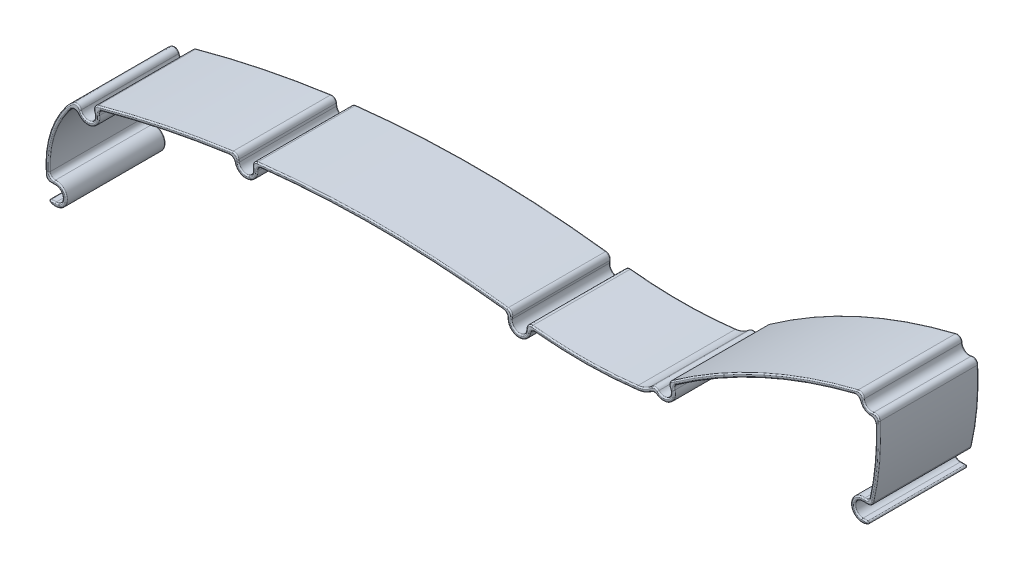
SolidWorks part; units mm, degrees
material "ﾎﾟﾘｴﾁﾚﾝﾃﾚﾌﾀﾗｰﾄ(PET)"
ref_plane "正面" through (0, 0, 0) normal (0, 0, 1) x (1, 0, 0)
ref_plane "平面" through (0, 0, 0) normal (0, 1, 0) x (1, 0, 0)
ref_plane "右側面" through (0, 0, 0) normal (1, 0, 0) x (0, 0, -1)
sketch "ｽｹｯﾁ1" plane through (0, 0, 0) normal (0, 0, 1) x (1, 0, 0)
  line L0 (152.9752, 59.7355) -> (155.8598, 58.9115) construction
  line L2 (-22.5, -19) -> (22.5, -19)
  line L6 (150, 3) -> (150, 12)
  circle A0 centre (152.9752, 59.7355) radius 3 construction
  arc A25 (145.1217, 33.8719) -> (159.4857, 98.9896) centre (52.35, 88.479) ccw
  arc A26 (159.4857, 98.9896) -> (155.8531, 101.6261) centre (156.5, 98.6967) ccw
  arc A27 (155.8531, 101.6261) -> (74.5652, 65.2106) centre (203.2901, -113.1988) ccw
  arc A28 (73.7195, 65.056) -> (74.5652, 65.2106) centre (73.98, 66.0215) ccw
  arc A29 (73.7195, 65.056) -> (74.5652, 65.2106) centre (73.98, 66.0215) ccw
  arc A30 (73.7195, 65.056) -> (69.9392, 62.246) centre (72.938, 62.1596) ccw
  arc A31 (73.7195, 65.056) -> (69.9392, 62.246) centre (72.938, 62.1596) ccw
  arc A32 (62.3481, 57.6959) -> (67.3326, 59.7624) centre (61.1527, 67.6242) ccw
  arc A33 (15.0718, 58.0612) -> (62.3481, 57.6959) centre (40.1338, 242.1889) ccw
  arc A34 (15.0718, 58.0612) -> (-159.8291, 45.3832) centre (-42.29, -363.3692) ccw
  arc A35 (-159.8291, 45.3832) -> (-168.029, 39.7531) centre (-155.4945, 30.2837) ccw
  arc A36 (-168.029, 39.7531) -> (-174.9177, 6.802) centre (-136.5587, 15.9784) ccw
  arc A37 (-174.9177, 6.802) -> (-172, 4.5) centre (-172, 7.5) ccw
  arc A38 (-128.5711, -10.4869) -> (-172, 4.5) centre (-172, -65.9175) ccw
  arc A39 (-128.5711, -10.4869) -> (-89, -16.1206) centre (-103.9017, 21) ccw
  arc A40 (-24.2684, -18.5879) -> (-89, -16.1206) centre (-59.3978, -89.8605) ccw
  arc A41 (-24.2684, -18.5879) -> (-22.5, -19) centre (-22.5, -15) ccw
  arc A42 (95.4808, -24.1793) -> (22.5, -19) centre (22.5, -535.7727) ccw
  arc A43 (95.4808, -24.1793) -> (100, -24.5) centre (100, 7.5) ccw
  arc A44 (100, -24.5) -> (140.9896, -3.1331) centre (100, 25.5) ccw
  arc A45 (147, 0) -> (140.9896, -3.1331) centre (147, -7.3316) ccw
  arc A48 (69.5475, 61.4807) -> (69.9392, 62.246) centre (68.9396, 62.2747) ccw
  arc A49 (145.1217, 33.8719) -> (140.5409, 25.3936) centre (258.447, -32.8336) ccw
  arc A50 (155.8598, 58.9115) -> (159.4857, 98.9896) centre (52.35, 88.479) ccw
  arc A51 (159.4857, 98.9896) -> (155.8531, 101.6261) centre (156.5, 98.6967) ccw
  arc A52 (155.8531, 101.6261) -> (74.5652, 65.2106) centre (203.2901, -113.1988) ccw
  arc A53 (69.5475, 61.4807) -> (69.9392, 62.246) centre (68.9396, 62.2747) ccw
  arc A54 (69.5475, 61.4807) -> (67.3326, 59.7624) centre (203.2901, -113.1988) ccw
  arc A55 (69.5475, 61.4807) -> (67.3326, 59.7624) centre (203.2901, -113.1988) ccw
  arc A56 (140.5409, 25.3936) -> (147, 15) centre (147, 22.2038) ccw
  arc A57 (62.3481, 57.6959) -> (67.3326, 59.7624) centre (61.1527, 67.6242) ccw
  arc A58 (15.0718, 58.0612) -> (62.3481, 57.6959) centre (40.1338, 242.1889) ccw
  arc A59 (15.0718, 58.0612) -> (-159.8291, 45.3832) centre (-42.29, -363.3692) ccw
  arc A60 (-159.8291, 45.3832) -> (-168.029, 39.7531) centre (-155.4945, 30.2837) ccw
  arc A61 (-168.029, 39.7531) -> (-174.9177, 6.802) centre (-136.5587, 15.9784) ccw
  arc A86 (147, 0) -> (150, 3) centre (147, 3) ccw
  arc A87 (150, 12) -> (147, 15) centre (147, 12) ccw
  dimension "D1" = 0
extrude "押し出し-薄板1" add sketch "ｽｹｯﾁ1" along normal up to surface (40 mm away) thin thin type one direction reverse wall 1.5
sketch "ｽｹｯﾁ2" plane through (0, 0, 0) normal (0, 0, 1) x (1, 0, 0)
  circle A0 centre (156.5, 98.6967) radius 3 construction
  circle A1 centre (152.9752, 59.7355) radius 3 construction
  circle A2 centre (72.938, 62.1596) radius 3 construction
  circle A3 centre (14.6672, 55.0886) radius 3 construction
  circle A4 centre (-95.3328, 55.6027) radius 3 construction
  circle A5 centre (-159, 42.5) radius 3 construction
  circle A6 centre (-172, 7.5) radius 3 construction
  circle A7 centre (156.5, 98.6967) radius 3
  circle A8 centre (152.9752, 59.7355) radius 3
  circle A9 centre (72.938, 62.1596) radius 3
  circle A10 centre (14.6672, 55.0886) radius 3
  circle A11 centre (-95.3328, 55.6027) radius 3
  circle A12 centre (-159, 42.5) radius 3
  circle A13 centre (-172, 7.5) radius 3
extrude "ﾎﾞｽ - 押し出し1" add sketch "ｽｹｯﾁ2" along normal through all
sketch "ｽｹｯﾁ3" plane through (0, 0, 40) normal (0, 0, 1) x (1, 0, 0)
  circle A0 centre (-172, 7.5) radius 4.5
  circle A1 centre (-159, 42.5) radius 4.5
  circle A2 centre (-95.3328, 55.6027) radius 4.5
  circle A3 centre (14.6672, 55.0886) radius 4.5
  circle A4 centre (72.938, 62.1596) radius 4.5
  circle A5 centre (156.5, 98.6967) radius 4.5
  circle A6 centre (152.9752, 59.7355) radius 4.5
  arc A17 (-168.029, 39.7531) -> (-174.9177, 6.802) centre (-136.5587, 15.9784) ccw
  arc A18 (-168.029, 39.7531) -> (-174.9177, 6.802) centre (-136.5587, 15.9784) ccw
  arc A19 (-174.9177, 6.802) -> (-173.9852, 9.7492) centre (-172, 7.5) ccw
  arc A20 (-174.9177, 6.802) -> (-173.9852, 9.7492) centre (-172, 7.5) ccw
  arc A41 (-166.8321, 38.8489) -> (-173.9852, 9.7492) centre (-136.5587, 15.9784) ccw
  arc A42 (-166.8321, 38.8489) -> (-173.9852, 9.7492) centre (-136.5587, 15.9784) ccw
  arc A43 (-161.9687, 42.9324) -> (-166.8321, 38.8489) centre (-155.4945, 30.2837) ccw
  arc A44 (-161.9687, 42.9324) -> (-166.8321, 38.8489) centre (-155.4945, 30.2837) ccw
  arc A45 (-161.9687, 42.9324) -> (-156.911, 44.6532) centre (-159, 42.5) ccw
  arc A46 (17.4359, 56.2436) -> (62.5274, 56.2067) centre (40.1338, 242.1889) ccw
  arc A47 (62.5274, 56.2067) -> (68.2596, 58.5831) centre (61.1527, 67.6242) ccw
  arc A48 (70.4594, 60.2897) -> (68.2596, 58.5831) centre (203.2901, -113.1988) ccw
  arc A49 (70.4594, 60.2897) -> (70.5413, 60.3552) centre (68.9396, 62.2747) ccw
  arc A50 (-161.9687, 42.9324) -> (-156.911, 44.6532) centre (-159, 42.5) ccw
  arc A51 (-98.1023, 56.756) -> (-156.911, 44.6532) centre (-42.29, -363.3692) ccw
  arc A52 (-98.1023, 56.756) -> (-156.911, 44.6532) centre (-42.29, -363.3692) ccw
  arc A53 (-98.1023, 56.756) -> (-92.9382, 57.4098) centre (-95.3328, 55.6027) ccw
  arc A54 (-98.1023, 56.756) -> (-92.9382, 57.4098) centre (-95.3328, 55.6027) ccw
  arc A55 (12.2895, 56.918) -> (-92.9382, 57.4098) centre (-42.29, -363.3692) ccw
  arc A56 (12.2895, 56.918) -> (-92.9382, 57.4098) centre (-42.29, -363.3692) ccw
  arc A57 (12.2895, 56.918) -> (17.4359, 56.2436) centre (14.6672, 55.0886) ccw
  arc A58 (12.2895, 56.918) -> (17.4359, 56.2436) centre (14.6672, 55.0886) ccw
  arc A59 (70.5413, 60.3552) -> (75.3565, 63.9346) centre (72.938, 62.1596) ccw
  arc A60 (70.5413, 60.3552) -> (75.3565, 63.9346) centre (72.938, 62.1596) ccw
  arc A61 (69.5475, 61.4807) -> (69.9392, 62.246) centre (68.9396, 62.2747) ccw
  arc A62 (69.5475, 61.4807) -> (67.3326, 59.7624) centre (203.2901, -113.1988) ccw
  arc A63 (62.3481, 57.6959) -> (67.3326, 59.7624) centre (61.1527, 67.6242) ccw
  arc A64 (15.0718, 58.0612) -> (62.3481, 57.6959) centre (40.1338, 242.1889) ccw
  arc A65 (75.3565, 63.9346) -> (75.4428, 63.9941) centre (73.98, 66.0215) ccw
  arc A66 (75.3565, 63.9346) -> (75.4428, 63.9941) centre (73.98, 66.0215) ccw
  arc A67 (153.6343, 99.5841) -> (75.4428, 63.9941) centre (203.2901, -113.1988) ccw
  arc A68 (153.6343, 99.5841) -> (75.4428, 63.9941) centre (203.2901, -113.1988) ccw
  arc A69 (153.6343, 99.5841) -> (158.2162, 96.236) centre (156.5, 98.6967) ccw
  arc A70 (153.6343, 99.5841) -> (158.2162, 96.236) centre (156.5, 98.6967) ccw
  arc A71 (155.1051, 61.8482) -> (158.2162, 96.236) centre (52.35, 88.479) ccw
  arc A72 (155.1051, 61.8482) -> (158.2162, 96.236) centre (52.35, 88.479) ccw
  arc A73 (155.1051, 61.8482) -> (155.8598, 58.9115) centre (152.9752, 59.7355) ccw
  arc A74 (155.1051, 61.8482) -> (155.8598, 58.9115) centre (152.9752, 59.7355) ccw
  arc A75 (155.8598, 58.9115) -> (159.4857, 98.9896) centre (52.35, 88.479) ccw
  arc A76 (17.4359, 56.2436) -> (62.5274, 56.2067) centre (40.1338, 242.1889) ccw
  arc A77 (62.5274, 56.2067) -> (68.2596, 58.5831) centre (61.1527, 67.6242) ccw
  arc A78 (70.4594, 60.2897) -> (68.2596, 58.5831) centre (203.2901, -113.1988) ccw
  arc A79 (70.4594, 60.2897) -> (70.5413, 60.3552) centre (68.9396, 62.2747) ccw
  arc A80 (155.8598, 58.9115) -> (159.4857, 98.9896) centre (52.35, 88.479) ccw
  arc A81 (159.4857, 98.9896) -> (155.8531, 101.6261) centre (156.5, 98.6967) ccw
  arc A82 (159.4857, 98.9896) -> (155.8531, 101.6261) centre (156.5, 98.6967) ccw
  arc A83 (155.8531, 101.6261) -> (74.5652, 65.2106) centre (203.2901, -113.1988) ccw
  arc A84 (155.8531, 101.6261) -> (74.5652, 65.2106) centre (203.2901, -113.1988) ccw
  arc A85 (73.7195, 65.056) -> (74.5652, 65.2106) centre (73.98, 66.0215) ccw
  arc A86 (73.7195, 65.056) -> (74.5652, 65.2106) centre (73.98, 66.0215) ccw
  arc A87 (73.7195, 65.056) -> (69.9392, 62.246) centre (72.938, 62.1596) ccw
  arc A88 (73.7195, 65.056) -> (69.9392, 62.246) centre (72.938, 62.1596) ccw
  arc A89 (15.0718, 58.0612) -> (-159.8291, 45.3832) centre (-42.29, -363.3692) ccw
  arc A90 (15.0718, 58.0612) -> (-159.8291, 45.3832) centre (-42.29, -363.3692) ccw
  arc A91 (69.5475, 61.4807) -> (69.9392, 62.246) centre (68.9396, 62.2747) ccw
  arc A92 (69.5475, 61.4807) -> (67.3326, 59.7624) centre (203.2901, -113.1988) ccw
  arc A93 (62.3481, 57.6959) -> (67.3326, 59.7624) centre (61.1527, 67.6242) ccw
  arc A94 (15.0718, 58.0612) -> (62.3481, 57.6959) centre (40.1338, 242.1889) ccw
  arc A95 (-159.8291, 45.3832) -> (-168.029, 39.7531) centre (-155.4945, 30.2837) ccw
  arc A96 (-159.8291, 45.3832) -> (-168.029, 39.7531) centre (-155.4945, 30.2837) ccw
  arc M31 (-168.029, 39.7531) -> (-174.9177, 6.802) centre (-136.5587, 15.9784) ccw
  arc M32 (-174.9177, 6.802) -> (-173.9852, 9.7492) centre (-172, 7.5) ccw
  arc M33 (-173.9852, 9.7492) -> (-166.8321, 38.8489) centre (-136.5587, 15.9784) cw
  arc M34 (-166.8321, 38.8489) -> (-161.9687, 42.9324) centre (-155.4945, 30.2837) cw
  arc M35 (-161.9687, 42.9324) -> (-156.911, 44.6532) centre (-159, 42.5) ccw
  arc M36 (-156.911, 44.6532) -> (-98.1023, 56.756) centre (-42.29, -363.3692) cw
  arc M37 (-98.1023, 56.756) -> (-92.9382, 57.4098) centre (-95.3328, 55.6027) ccw
  arc M38 (-92.9382, 57.4098) -> (12.2895, 56.918) centre (-42.29, -363.3692) cw
  arc M39 (12.2895, 56.918) -> (17.4359, 56.2436) centre (14.6672, 55.0886) ccw
  arc M40 (17.4359, 56.2436) -> (62.5274, 56.2067) centre (40.1338, 242.1889) ccw
  arc M42 (68.2596, 58.5831) -> (70.4594, 60.2897) centre (203.2901, -113.1988) cw
  arc M43 (70.4594, 60.2897) -> (70.5413, 60.3552) centre (68.9396, 62.2747) ccw
  arc M44 (70.5413, 60.3552) -> (75.3565, 63.9346) centre (72.938, 62.1596) ccw
  arc M45 (75.3565, 63.9346) -> (75.4428, 63.9941) centre (73.98, 66.0215) ccw
  arc M46 (75.4428, 63.9941) -> (153.6343, 99.5841) centre (203.2901, -113.1988) cw
  arc M47 (153.6343, 99.5841) -> (158.2162, 96.236) centre (156.5, 98.6967) ccw
  arc M48 (158.2162, 96.236) -> (155.1051, 61.8482) centre (52.35, 88.479) cw
  arc M49 (155.1051, 61.8482) -> (155.8598, 58.9115) centre (152.9752, 59.7355) ccw
  arc M50 (155.8598, 58.9115) -> (159.4857, 98.9896) centre (52.35, 88.479) ccw
  dimension "D1" = 9
  dimension "D2" = 0
extrude "ﾎﾞｽ - 押し出し2" add sketch "ｽｹｯﾁ3" against normal through all contours A6 M48 M50 M49 | A5 M46 M48 M47 | A4 M42 M46 M45 M44 M43 | A3 M38 M40 M39 | A2 M36 M38 M37 | A1 M34 M36 M35 | A0 M31 M33 M32 region at (-173.3991, 3.3572, 40) region at (-162.678, 42.4107, 40) region at (-98.9039, 56.5367, 40) region at (11.4584, 56.9129, 40) region at (69.9721, 59.7793, 40) region at (154.707, 96.2487, 40) region at (155.1864, 62.6817, 40)
sketch "ｽｹｯﾁ4" plane through (0, 0, 40) normal (0, 0, 1) x (1, 0, 0)
  line L0 (-159, 42.5) -> (-159.8361, 45.3811) construction
  line L1 (-161.8811, 41.6639) -> (-162.7173, 44.545)
  line L2 (-156.1189, 43.3361) -> (-156.955, 46.2173)
  line L3 (-172, 7.5) -> (-176.5, 7.5) construction
  line L4 (-172, 4.5) -> (-176.5, 4.5)
  line L5 (-172, 10.5) -> (-176.5, 10.5)
  line L6 (-95.3328, 55.6027) -> (-95.7096, 58.579) construction
  line L7 (-98.3091, 55.2259) -> (-98.6859, 58.2022)
  line L8 (-92.3566, 55.9795) -> (-92.7334, 58.9558)
  line L9 (14.6672, 55.0886) -> (15.0718, 58.0612) construction
  line L10 (11.6946, 55.4932) -> (12.0992, 58.4658)
  line L11 (17.6397, 54.684) -> (18.0444, 57.6566)
  line L12 (72.938, 62.1596) -> (71.1482, 64.5673) construction
  line L13 (70.5303, 60.3699) -> (68.7406, 62.7776)
  line L14 (75.3456, 63.9494) -> (73.5559, 66.357)
  line L15 (156.5, 98.6967) -> (158.2622, 101.1246) construction
  line L16 (154.0721, 100.4589) -> (155.8343, 102.8868)
  line L17 (158.9279, 96.9345) -> (160.6901, 99.3624)
  line L18 (152.9752, 59.7355) -> (157.4752, 59.7355) construction
  line L19 (152.9752, 62.7355) -> (157.4752, 62.7355)
  line L20 (152.9752, 56.7355) -> (157.4752, 56.7355)
  line L21 (-99.735, 56.5359) -> (-91.3021, 57.6035) construction
  arc A0 (15.0718, 58.0612) -> (-159.8291, 45.3832) centre (-42.29, -363.3692) ccw construction
  arc A1 (-159.8291, 45.3832) -> (-168.029, 39.7531) centre (-155.4945, 30.2837) ccw construction
  arc A2 (-161.8811, 41.6639) -> (-156.1189, 43.3361) centre (-159, 42.5) ccw
  arc A3 (-156.955, 46.2173) -> (-162.7173, 44.545) centre (-159.8361, 45.3811) ccw
  arc A4 (-172, 4.5) -> (-172, 10.5) centre (-172, 7.5) ccw
  arc A5 (-176.5, 10.5) -> (-176.5, 4.5) centre (-176.5, 7.5) ccw
  arc A6 (-98.3091, 55.2259) -> (-92.3566, 55.9795) centre (-95.3328, 55.6027) ccw
  arc A7 (-92.7334, 58.9558) -> (-98.6859, 58.2022) centre (-95.7096, 58.579) ccw
  arc A8 (15.0718, 58.0612) -> (62.3481, 57.6959) centre (40.1338, 242.1889) ccw construction
  arc A9 (11.6946, 55.4932) -> (17.6397, 54.684) centre (14.6672, 55.0886) ccw
  arc A10 (18.0444, 57.6566) -> (12.0992, 58.4658) centre (15.0718, 58.0612) ccw
  circle A11 centre (72.938, 62.1596) radius 3 construction
  arc A12 (70.5303, 60.3699) -> (75.3456, 63.9494) centre (72.938, 62.1596) ccw
  arc A13 (73.5559, 66.357) -> (68.7406, 62.7776) centre (71.1482, 64.5673) ccw
  circle A14 centre (156.5, 98.6967) radius 3 construction
  arc A15 (154.0721, 100.4589) -> (158.9279, 96.9345) centre (156.5, 98.6967) ccw
  arc A16 (160.6901, 99.3624) -> (155.8343, 102.8868) centre (158.2622, 101.1246) ccw
  arc A17 (155.5082, 63.4549) -> (156.7424, 62.1969) centre (152.9752, 59.7355) ccw construction
  arc A18 (152.9752, 62.7355) -> (152.9752, 56.7355) centre (152.9752, 59.7355) ccw
  arc A19 (157.4752, 56.7355) -> (157.4752, 62.7355) centre (157.4752, 59.7355) ccw
  arc A20 (-175.5786, 10.2283) -> (-174.2242, 11.4119) centre (-172, 7.5) ccw construction
  point P12 (-159.4181, 43.9406)
  point P19 (-174.25, 7.5)
  point P29 (-95.5212, 57.0909)
  point P37 (14.8695, 56.5749)
  point P48 (72.0431, 63.3635)
  point P59 (157.3811, 99.9106)
  point P70 (155.2252, 59.7355)
  dimension "D1" = 6
extrude "ｶｯﾄ - 押し出し2" cut sketch "ｽｹｯﾁ4" against normal through all
fillet "ﾌｨﾚｯﾄ1" radius 2 24 edges at (-174.2242, 11.4119, 20) (-155.3241, 45.0957, 20) (-99.735, 56.5359, 20) (-91.3021, 57.6035, 20) (10.6553, 57.127, 20) (19.0628, 56.0522, 20) (69.3543, 59.438, 20) (76.5769, 64.8069, 20) (152.0286, 99.203, 20) (158.3244, 94.5831, 20) (155.5082, 63.4549, 20) (156.8765, 62.7355, 20) (159.5915, 97.8487, 20) (154.7384, 101.3769, 20) (74.4582, 65.1432, 20) (69.6428, 61.5638, 20) (18.0475, 57.6806, 20) (12.0977, 58.4553, 20) (-92.7321, 58.9453, 20) (-98.6846, 58.1917, 20) (-156.95, 46.2001, 20) (-162.6387, 44.2745, 20) (-175.6177, 10.5, 20) (-163.4764, 42.0393, 20)
fillet "ﾌｨﾚｯﾄ3" radius 0.5 2 edges at (156.3293, 56.7355, 20) (-175.3541, 4.5, 20)
fillet "ﾌｨﾚｯﾄ4" radius 0.5 134 edges at (149.9752, 59.7355, 0) (154.1363, 62.7355, 0) (156.5426, 63.1705, 0) (159.5859, 79.0461, 0) (159.0267, 95.5112, 0) (154.7232, 96.2795, 0) (152.7152, 100.1504, 0) (111.9498, 86.9435, 0) (75.3032, 65.1007, 0) (74.7277, 59.752, 0) (69.44, 60.7423, 0) (67.6924, 60.0446, 0) (64.9824, 58.3866, 0) (41.1719, 56.3663, 0) (18.5337, 57.0468, 0) (17.7117, 55.2124, 0) (14.2625, 52.116, 0) (11.76, 55.974, 0) (11.4286, 57.9445, 0) (-40.302, 61.9424, 0) (-92.0677, 58.4282, 0) (-92.4175, 56.4609, 0) (-94.956, 52.6265, 0) (-98.37, 55.7073, 0) (-99.1991, 57.5254, 0) (-128.0248, 53.2163, 0) (-156.2106, 45.7903, 0) (-156.2524, 43.7963, 0) (-158.1639, 39.6189, 0) (-161.891, 41.6978, 0) (-163.1966, 43.0742, 0) (-166.6348, 41.3596, 0) (-174.4968, 26.7635, 0) (-175.185, 11.0216, 0) (-172.919, 10.5, 0) (-169, 7.5, 0) (-172.9682, 4.5, 0) (-174.4206, 4.125, 0) (-167.6069, 6.5248, 0) (-173.7686, 12.4857, 0) (-172.8528, 27.0365, 0) (-166.3071, 39.5028, 0) (-164.1538, 40.734, 0) (-157.2222, 38.3661, 0) (-154.323, 44.8162, 0) (-127.7213, 51.7473, 0) (-100.5444, 55.8838, 0) (-94.7676, 51.1384, 0) (-90.3558, 57.1737, 0) (-40.309, 60.4424, 0) (9.705, 56.706, 0) (14.1156, 50.6225, 0) (19.8537, 55.4356, 0) (41.8972, 54.8717, 0) (65.4296, 56.9491, 0) (69.2025, 58.814, 0) (75.6214, 58.5473, 0) (77.2276, 64.7931, 0) (112.4002, 85.5002, 0) (151.2798, 98.4666, 0) (153.8276, 95.0762, 0) (157.8297, 93.6291, 0) (158.0682, 78.9148, 0) (155.1928, 64.4822, 0) (148.5382, 58.985, 0) (155.3958, 56.3605, 0) (153.9435, 56.7355, 0) (155.1928, 64.4822, 40) (158.0682, 78.9148, 40) (157.8297, 93.6291, 40) (153.8276, 95.0762, 40) (151.2798, 98.4666, 40) (112.4002, 85.5002, 40) (77.2276, 64.7931, 40) (75.6214, 58.5473, 40) (69.2025, 58.814, 40) (65.4296, 56.9491, 40) (41.8972, 54.8717, 40) (19.8537, 55.4356, 40) (14.1156, 50.6225, 40) (9.705, 56.706, 40) (-40.309, 60.4424, 40) (-90.3558, 57.1737, 40) (-94.7676, 51.1384, 40) (-100.5444, 55.8838, 40) (-127.7213, 51.7473, 40) (-154.323, 44.8162, 40) (-157.2222, 38.3661, 40) (-164.1538, 40.734, 40) (-166.3071, 39.5028, 40) (-172.8528, 27.0365, 40) (-173.7686, 12.4857, 40) (-167.6069, 6.5248, 40) (-174.4206, 4.125, 40) (-172.9682, 4.5, 40) (-169, 7.5, 40) (-172.919, 10.5, 40) (-175.185, 11.0216, 40) (-174.4968, 26.7635, 40) (-166.6348, 41.3596, 40) (-163.1966, 43.0742, 40) (-161.891, 41.6978, 40) (-158.1639, 39.6189, 40) (-156.2524, 43.7963, 40) (-156.2106, 45.7903, 40) (-128.0248, 53.2163, 40) (-99.1991, 57.5254, 40) (-98.37, 55.7073, 40) (-94.956, 52.6265, 40) (-92.4175, 56.4609, 40) (-92.0677, 58.4282, 40) (-40.302, 61.9424, 40) (11.4286, 57.9445, 40) (11.76, 55.974, 40) (14.2625, 52.116, 40) (17.7117, 55.2124, 40) (18.5337, 57.0468, 40) (41.1719, 56.3663, 40) (64.9824, 58.3866, 40) (67.6924, 60.0446, 40) (69.44, 60.7423, 40) (74.7277, 59.752, 40) (75.3032, 65.1007, 40) (111.9498, 86.9435, 40) (152.7152, 100.1504, 40) (154.7232, 96.2795, 40) (159.0267, 95.5112, 40) (159.5859, 79.0461, 40) (156.5426, 63.1705, 40) (154.1363, 62.7355, 40) (149.9752, 59.7355, 40) (153.9435, 56.7355, 40) (155.3958, 56.3605, 40) (148.5382, 58.985, 40)
